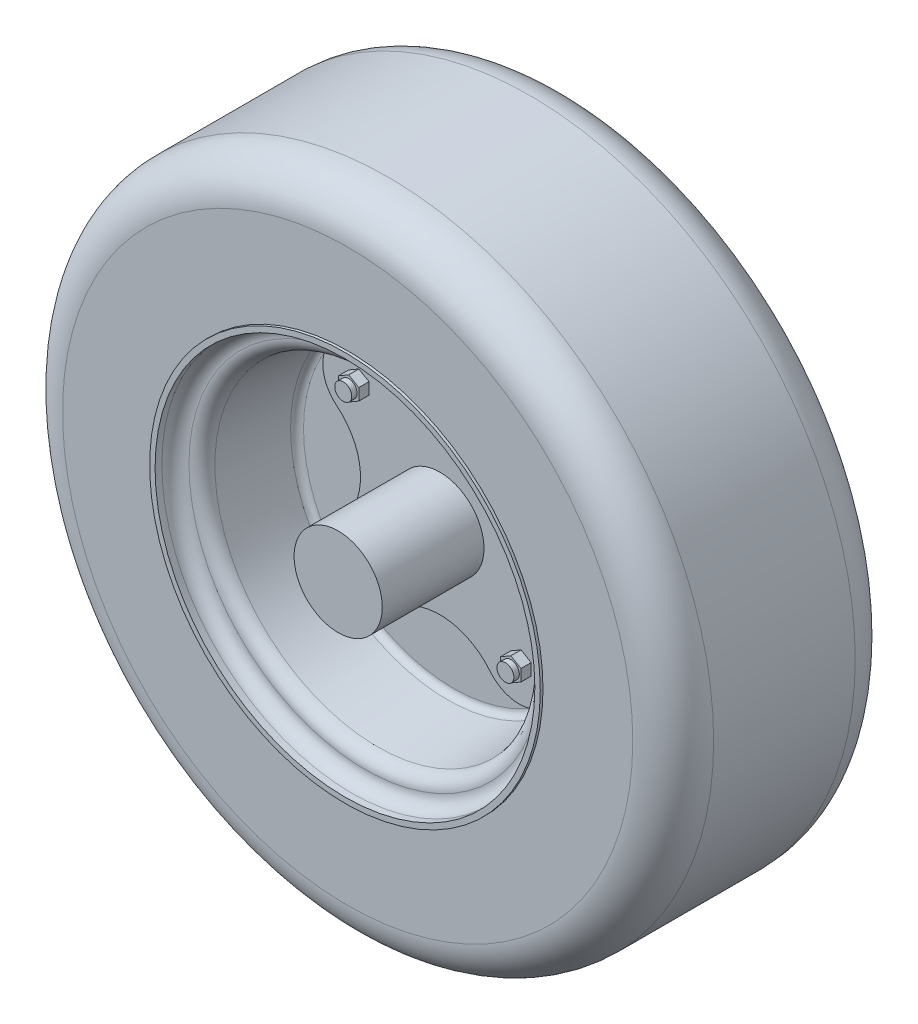
SolidWorks part; units mm, degrees
ref_plane "Front Plane" through (0, 0, 0) normal (0, 0, 1) x (1, 0, 0)
ref_plane "Top Plane" through (0, 0, 0) normal (0, 1, 0) x (1, 0, 0)
ref_plane "Right Plane" through (0, 0, 0) normal (1, 0, 0) x (0, 0, -1)
sketch "Sketch4" plane through (0, 0, 0) normal (0, 0, 1) x (1, 0, 0)
  line L0 (0, -6.35) -> (0, -27.1526) construction
  line L1 (0, -27.1526) -> (43.18, -27.1526)
  line L2 (43.18, -27.1526) -> (43.18, -16.0401)
  line L3 (43.18, -16.0401) -> (40.64, -16.0401)
  line L4 (40.64, -16.0401) -> (40.64, -13.5001)
  line L5 (40.64, -13.5001) -> (44.45, -13.5001)
  line L6 (44.45, -13.5001) -> (44.45, -6.35)
  line L7 (44.45, -6.35) -> (0, -6.35)
  line L9 (0, -6.35) -> (0, -27.1526)
  line L10 (-127.4196, -221.8568) -> (-28.4907, -27.1526) construction
  line L11 (-82.1304, -244.8682) -> (28.4907, -27.1526) construction
  line L12 (-104.775, -233.3625) -> (0, -27.1526) construction
  line L13 (0, 0) -> (0, -385.7625) construction
  circle A0 centre (-104.775, -233.3625) radius 152.4 construction
  arc A1 (-127.4196, -221.8568) -> (-82.1304, -244.8682) centre (-104.775, -233.3625) ccw construction
  point P13 (-104.775, -80.9625)
  point P14 (-104.775, -385.7625)
  dimension "Wheel Dia" = 304.8
  dimension "D7" = 50.8
  dimension "Mount Height" = 385.7625
  dimension "Offset" = 104.775
  dimension "D1" = 7.1501
  dimension "D2" = 11.1125
  dimension "D3" = 2.54
  dimension "D4" = 88.9
  dimension "D5" = 86.36
  dimension "D6" = 81.28
revolve "Revolve1" [suppressed] add sketch "Sketch4" angle 360 about L0
ref_plane "Plane1" through (-104.775, 0, 0) normal (1, 0, 0) x (0, 0, -1)
sketch "Sketch5" plane through (-104.775, 0, 0) normal (1, 0, 0) x (0, 0, -1)
  line L1 (-52.07, -80.9625) -> (52.07, -80.9625)
  line L2 (-52.07, -80.9625) -> (-52.07, -385.7625)
  line L3 (-52.07, -385.7625) -> (52.07, -385.7625)
  line L4 (52.07, -80.9625) -> (52.07, -385.7625)
  dimension "Wheel Width" = 104.14
sketch "Sketch6" plane through (-104.775, 0, 0) normal (1, 0, 0) x (0, 0, -1)
  line L0 (-52.07, -141.9225) -> (-52.07, -99.897)
  line L1 (-33.1355, -80.9625) -> (-28.9935, -80.9625)
  line L2 (52.07, -99.897) -> (52.07, -141.9225)
  line L3 (-52.07, -80.9625) -> (52.07, -80.9625) construction
  line L4 (-52.07, -80.9625) -> (-52.07, -385.7625) construction
  line L5 (52.07, -80.9625) -> (52.07, -385.7625) construction
  line L6 (-111.1453, -233.3625) -> (111.1453, -233.3625) construction
  line L7 (-52.07, -141.9225) -> (-53.34, -141.9225)
  line L8 (-53.34, -141.9225) -> (-53.34, -144.4625)
  line L9 (-53.34, -212.725) -> (-56.515, -212.725)
  line L10 (-56.515, -212.725) -> (-56.515, -233.3625)
  line L11 (0, -80.9625) -> (0, -256.5466) construction
  line L12 (0, -80.9625) -> (0, -385.7625) construction
  line L13 (56.515, -212.725) -> (56.515, -233.3625)
  line L14 (53.34, -212.725) -> (56.515, -212.725)
  line L15 (28.9935, -80.9625) -> (20.7097, -80.9625)
  line L16 (12.4258, -80.9625) -> (4.1419, -80.9625)
  line L17 (-56.515, -233.3625) -> (56.515, -233.3625)
  line L18 (-28.9935, -80.9625) -> (-28.9935, -83.3438) construction
  line L19 (-28.9935, -83.3438) -> (-20.7097, -83.3438) construction
  line L20 (-20.7097, -83.3438) -> (-20.7097, -80.9625) construction
  line L21 (-12.4258, -80.9625) -> (-12.4258, -83.3438) construction
  line L22 (-12.4258, -83.3438) -> (-4.1419, -83.3438) construction
  line L23 (-4.1419, -83.3438) -> (-4.1419, -80.9625) construction
  line L24 (4.1419, -83.3438) -> (4.1419, -80.9625) construction
  line L25 (12.4258, -83.3438) -> (4.1419, -83.3438) construction
  line L26 (12.4258, -80.9625) -> (12.4258, -83.3438) construction
  line L27 (20.7097, -83.3438) -> (20.7097, -80.9625) construction
  line L28 (28.9935, -83.3438) -> (20.7097, -83.3438) construction
  line L29 (28.9935, -80.9625) -> (28.9935, -83.3438) construction
  line L30 (-20.7097, -80.9625) -> (-12.4258, -80.9625)
  line L31 (-4.1419, -80.9625) -> (4.1419, -80.9625)
  line L32 (12.4258, -80.9625) -> (20.7097, -80.9625)
  line L33 (28.9935, -80.9625) -> (33.1355, -80.9625)
  line L34 (-53.34, -144.4625) -> (-50.165, -144.4625)
  line L35 (-38.0184, -157.1383) -> (-5.4383, -159.9887)
  line L36 (-2.54, -163.1516) -> (-2.54, -212.725)
  line L37 (-43.815, -150.8125) -> (-43.815, -208.9815) construction
  line L38 (-53.34, -212.725) -> (-2.54, -212.725)
  line L39 (53.34, -212.725) -> (2.54, -212.725)
  line L40 (2.54, -163.1516) -> (2.54, -212.725)
  line L41 (38.0184, -157.1383) -> (5.4383, -159.9887)
  line L42 (53.34, -144.4625) -> (50.165, -144.4625)
  line L43 (53.34, -141.9225) -> (53.34, -144.4625)
  line L44 (52.07, -141.9225) -> (53.34, -141.9225)
  line L45 (-4.1419, -80.9625) -> (-12.4258, -80.9625)
  line L46 (-20.7097, -80.9625) -> (-28.9935, -80.9625)
  arc A0 (-52.07, -99.897) -> (-33.1355, -80.9625) centre (-33.1355, -99.897) cw
  arc A1 (33.1355, -80.9625) -> (52.07, -99.897) centre (33.1355, -99.897) cw
  arc A2 (-50.165, -144.4625) -> (-43.815, -150.8125) centre (-50.165, -150.8125) cw
  arc A3 (-43.815, -150.8125) -> (-38.0184, -157.1383) centre (-37.465, -150.8125) ccw
  arc A4 (-5.4383, -159.9887) -> (-2.54, -163.1516) centre (-5.715, -163.1516) cw
  arc A5 (5.4383, -159.9887) -> (2.54, -163.1516) centre (5.715, -163.1516) ccw
  arc A6 (43.815, -150.8125) -> (38.0184, -157.1383) centre (37.465, -150.8125) cw
  arc A7 (50.165, -144.4625) -> (43.815, -150.8125) centre (50.165, -150.8125) ccw
  dimension "D1" = 18.9345
  dimension "D13" = 6.35
  dimension "D16" = 3.175
  dimension "D2" = 1.27
  dimension "D3" = 3.175
  dimension "D4" = 41.275
  dimension "D5" = 182.88
  dimension "D6" = 66.2709
  dimension "D7" = 8.2839
  dimension "D8" = 2.3813
  dimension "D9" = 8.2839
  dimension "D10" = 4.1419
  dimension "D11" = 3.175
  dimension "D12" = 2.54
  dimension "D14" = 5
  dimension "D15" = 2.54
revolve "Revolve2" add sketch "Sketch6" angle 360 about L6
sketch "Sketch13" plane through (0, 0, 2.54) normal (0, 0, 1) x (1, 0, 0)
  line L0 (-104.775, -212.725) -> (-104.775, -163.1516) construction
  line L1 (-104.775, -233.3625) -> (-154.4216, -183.7159) construction
  line L2 (-104.775, -233.3625) -> (-60.3899, -233.3625) construction
  circle A0 centre (-104.775, -233.3625) radius 70.2109 construction
  circle A1 centre (-104.775, -233.3625) radius 20.6375
  circle A2 centre (-104.775, -233.3625) radius 20.6375 construction
  circle A4 centre (-104.775, -233.3625) radius 70.2109 construction
  circle A6 centre (-104.775, -233.3625) radius 37.162 construction
  circle A7 centre (-104.775, -233.3625) radius 53.6864 construction
  arc A8 (-153.0787, -209.9321) -> (-128.2054, -185.0588) centre (-141.9195, -196.218) cw
  arc A9 (-128.2054, -185.0588) -> (-81.3446, -185.0588) centre (-104.775, -165.9934) ccw
  arc A10 (-81.3446, -185.0588) -> (-56.4713, -209.9321) centre (-67.6305, -196.218) cw
  arc A11 (-153.0787, -209.9321) -> (-153.0787, -256.7929) centre (-172.1441, -233.3625) cw
  arc A12 (-56.4713, -209.9321) -> (-56.4713, -256.7929) centre (-37.4059, -233.3625) ccw
  arc A13 (-153.0787, -256.7929) -> (-128.2054, -281.6662) centre (-141.9195, -270.507) ccw
  arc A15 (-81.3446, -281.6662) -> (-56.4713, -256.7929) centre (-67.6305, -270.507) ccw
  arc A16 (-128.2054, -281.6662) -> (-81.3446, -281.6662) centre (-104.775, -300.7316) cw
  point P8 (-104.775, -196.2005)
  point P9 (-104.775, -179.6761)
  dimension "D2" = 49.5734
  dimension "D3" = 16.5245
  dimension "D4" = 16.5245
  dimension "D5" = 45
extrude "Boss-Extrude5" add sketch "Sketch13" along normal blind 6.35
sketch "Sketch14" plane through (0, 0, 8.89) normal (0, 0, 1) x (1, 0, 0)
  line L0 (-104.775, -233.3625) -> (-154.4216, -183.7159) construction
  line L1 (-142.737, -200.8997) -> (-137.9745, -198.1501)
  line L2 (-137.9745, -198.1501) -> (-137.9745, -192.6509)
  line L3 (-137.9745, -192.6509) -> (-142.737, -189.9012)
  line L4 (-142.737, -189.9012) -> (-147.4995, -192.6509)
  line L5 (-147.4995, -192.6509) -> (-147.4995, -198.1501)
  line L6 (-147.4995, -198.1501) -> (-142.737, -200.8997)
  line L7 (-104.775, -233.3625) -> (-104.775, -136.2548) construction
  line L8 (-104.775, -233.3625) -> (-63.5, -233.3625) construction
  line L9 (-62.0505, -198.1501) -> (-66.813, -200.8997)
  line L10 (-62.0505, -192.6509) -> (-62.0505, -198.1501)
  line L11 (-66.813, -189.9012) -> (-62.0505, -192.6509)
  line L12 (-71.5755, -192.6509) -> (-66.813, -189.9012)
  line L13 (-71.5755, -198.1501) -> (-71.5755, -192.6509)
  line L14 (-66.813, -200.8997) -> (-71.5755, -198.1501)
  line L15 (-66.813, -265.8253) -> (-71.5755, -268.5749)
  line L16 (-71.5755, -268.5749) -> (-71.5755, -274.0741)
  line L17 (-71.5755, -274.0741) -> (-66.813, -276.8238)
  line L18 (-66.813, -276.8238) -> (-62.0505, -274.0741)
  line L19 (-62.0505, -274.0741) -> (-62.0505, -268.5749)
  line L20 (-62.0505, -268.5749) -> (-66.813, -265.8253)
  line L21 (-147.4995, -268.5749) -> (-142.737, -265.8253)
  line L22 (-147.4995, -274.0741) -> (-147.4995, -268.5749)
  line L23 (-142.737, -276.8238) -> (-147.4995, -274.0741)
  line L24 (-137.9745, -274.0741) -> (-142.737, -276.8238)
  line L25 (-137.9745, -268.5749) -> (-137.9745, -274.0741)
  line L26 (-142.737, -265.8253) -> (-137.9745, -268.5749)
  circle A0 centre (-142.737, -195.4005) radius 4.7625 construction
  circle A1 centre (-104.775, -233.3625) radius 53.6864 construction
  circle A3 centre (-66.813, -195.4005) radius 4.7625 construction
  circle A4 centre (-66.813, -271.3245) radius 4.7625 construction
  circle A5 centre (-142.737, -271.3245) radius 4.7625 construction
  dimension "D1" = 9.525
extrude "Boss-Extrude6" add sketch "Sketch14" along normal blind 4.7625
sketch "Sketch15" plane through (0, 0, 13.6525) normal (0, 0, 1) x (1, 0, 0)
  circle A0 centre (-142.737, -195.4005) radius 3.9687
  circle A1 centre (-66.813, -195.4005) radius 3.9687
  circle A2 centre (-142.737, -271.3245) radius 3.9687
  circle A3 centre (-66.813, -271.3245) radius 3.9687
  dimension "D1" = 7.9375
extrude "Boss-Extrude7" add sketch "Sketch15" along normal blind 2.54
sketch "Sketch16" plane through (0, 0, -2.54) normal (0, 0, -1) x (-1, 0, 0)
  circle A0 centre (66.813, -195.4005) radius 6.35
  circle A1 centre (142.737, -195.4005) radius 6.35
  circle A2 centre (142.737, -271.3245) radius 6.35
  circle A3 centre (66.813, -271.3245) radius 6.35
  dimension "D1" = 12.7
extrude "Boss-Extrude8" add sketch "Sketch16" along normal blind 4.7625
sketch "Sketch7" [suppressed] plane through (0, -27.1526, 0) normal (0, -1, 0) x (1, 0, 0)
  line L0 (-84.1375, 56.515) -> (-125.4125, 56.515) construction
  line L1 (-257.175, 65.405) -> (28.4907, 65.405)
  line L2 (-257.175, 65.405) -> (-257.175, -65.405)
  line L3 (-257.175, -65.405) -> (28.4907, -65.405)
  line L4 (28.4907, 65.405) -> (28.4907, -65.405)
  line L6 (-257.175, 33.1355) -> (-257.175, -33.1355) construction
  line L8 (28.4907, -65.405) -> (28.4907, 65.405) construction
  line L9 (-28.4907, 65.405) -> (-28.4907, -65.405) construction
  line L14 (-28.4907, 32.4468) -> (28.4907, 32.4468) construction
  line L15 (-28.4907, 32.4468) -> (-28.4907, 26.0968) construction
  line L16 (-28.4907, 26.0968) -> (28.4907, 26.0968) construction
  line L17 (28.4907, 32.4468) -> (28.4907, 26.0968) construction
  line L18 (-28.4907, -26.0968) -> (28.4907, -26.0968) construction
  line L19 (-28.4907, -26.0968) -> (-28.4907, -32.4468) construction
  line L20 (-28.4907, -32.4468) -> (28.4907, -32.4468) construction
  line L21 (28.4907, -26.0968) -> (28.4907, -32.4468) construction
  circle A0 centre (0, 0) radius 43.18 construction
  circle A1 centre (0, 0) radius 43.18 construction
  dimension "D1" = 8.89
  dimension "D3" = 6.35
extrude "Boss-Extrude2" [suppressed] add sketch "Sketch7" along normal up to vertex separate body up to point (-104.775, -385.7625, -52.07)
sketch "Sketch8" [suppressed] plane through (0, 0, 65.405) normal (0, 0, 1) x (1, 0, 0)
  line L0 (-127.4196, -221.8568) -> (-28.4907, -27.1526) construction
  line L1 (-82.1304, -244.8682) -> (28.4907, -27.1526) construction
  line L2 (-127.4196, -221.8568) -> (-28.4907, -27.1526)
  line L3 (-82.1304, -244.8682) -> (28.4907, -27.1526)
  arc A0 (-127.4196, -221.8568) -> (-82.1304, -244.8682) centre (-104.775, -233.3625) ccw construction
  arc A1 (-127.4196, -221.8568) -> (-82.1304, -244.8682) centre (-104.775, -233.3625) ccw
extrude "Cut-Extrude1" [suppressed] cut sketch "Sketch8" against normal through all and the other way through all flip side to cut
sketch "Sketch9" [suppressed] plane through (0, -144.3067, 0) normal (-1, 0, 0) x (0, 0, -1)
  line L0 (65.405, 241.4558) -> (65.405, -63.3442)
  line L2 (65.405, -117.1541) -> (-65.405, -117.1541) construction
  line L3 (26.0968, -117.1541) -> (59.055, -63.3442)
  line L4 (26.0968, -117.1541) -> (32.4468, -117.1541) construction
  line L5 (59.055, -63.3442) -> (59.055, 241.4558)
  line L6 (65.405, 241.4558) -> (59.055, 241.4558)
  line L7 (65.405, -117.1541) -> (65.405, 100.5615) construction
  line L8 (-52.07, 241.4558) -> (52.07, 241.4558) construction
  line L9 (65.405, -63.3442) -> (32.4468, -117.1541)
  line L10 (26.0968, -117.1541) -> (32.4468, -117.1541)
  line L11 (0, -144.3067) -> (0, 241.4558) construction
  line L12 (-26.0968, -117.1541) -> (-32.4468, -117.1541)
  line L13 (-65.405, -63.3442) -> (-32.4468, -117.1541)
  line L14 (-65.405, 241.4558) -> (-59.055, 241.4558)
  line L15 (-59.055, -63.3442) -> (-59.055, 241.4558)
  line L16 (-26.0968, -117.1541) -> (-59.055, -63.3442)
  line L17 (-65.405, 241.4558) -> (-65.405, -63.3442)
  dimension "D1" = 6.35
  dimension "D2" = 6.35
extrude "Cut-Extrude3" [suppressed] cut sketch "Sketch9" against normal through all and the other way through all flip side to cut
sketch "Sketch10" [suppressed] plane through (0, 0, 65.405) normal (0, 0, 1) x (1, 0, 0)
  line L1 (-104.775, -220.5309) -> (-115.8875, -226.9467)
  line L2 (-115.8875, -226.9467) -> (-115.8875, -239.7783)
  line L3 (-115.8875, -239.7783) -> (-104.775, -246.1941)
  line L4 (-104.775, -246.1941) -> (-93.6625, -239.7783)
  line L5 (-93.6625, -239.7783) -> (-93.6625, -226.9467)
  line L6 (-93.6625, -226.9467) -> (-104.775, -220.5309)
  circle A0 centre (-104.775, -233.3625) radius 11.1125 construction
  dimension "D1" = 22.225
extrude "Boss-Extrude3" [suppressed] add sketch "Sketch10" along normal blind 7.9375 separate body
sketch "Sketch11" [suppressed] plane through (0, 0, 73.3425) normal (0, 0, 1) x (1, 0, 0)
  circle A0 centre (-104.775, -233.3625) radius 11.1125 construction
  circle A1 centre (-104.775, -233.3625) radius 11.1125
extrude "Cut-Extrude4" [suppressed] cut sketch "Sketch11" against normal through all draft 60 flip side to cut
mirror "Mirror1" [suppressed] about plane through (0, 0, 0) normal (0, 0, 1) of bodies 113
sketch "Sketch12" [suppressed] plane through (0, 0, -59.055) normal (0, 0, 1) x (1, 0, 0)
  circle A0 centre (-104.775, -233.3625) radius 10.795
  dimension "D1" = 21.59
extrude "Boss-Extrude4" [suppressed] add sketch "Sketch12" along normal up to surface (118.11 mm away)
ref_axis "Center Axis 1" [suppressed] through (0, -37.5072, 0) along (0, 1, 0)
ref_plane "Plane2" [suppressed] through (18.3991, -223.2093, 0) normal (-0.0822, 0.9966, 0) x (-0.0727, -0.006, 0.9973)
sketch "Sketch17" [suppressed] plane through (18.3991, -223.2093, 0) normal (-0.0822, 0.9966, 0) x (-0.0727, -0.006, 0.9973)
  line L0 (-49.8795, -127.5714) -> (-49.8795, -170.5542) construction
  line L1 (-49.8795, -170.5542) -> (-49.8795, 348.1925) construction
equation "\"D5@Sketch6\" = \"Wheel Dia@Sketch4\"*.6"
equation "\"D1@Sketch6\" = \"Wheel Width@Sketch5\"/5.5"
equation "\"D7@Sketch6\" = \"D6@Sketch6\"/8"
equation "\"D9@Sketch6\" = \"D7@Sketch6\""
equation "\"D10@Sketch6\" = \"D7@Sketch6\"/2"
equation "\"D3@Sketch13\" = \"D2@Sketch13\"/3"
equation "\"D4@Sketch13\" = \"D3@Sketch13\""
